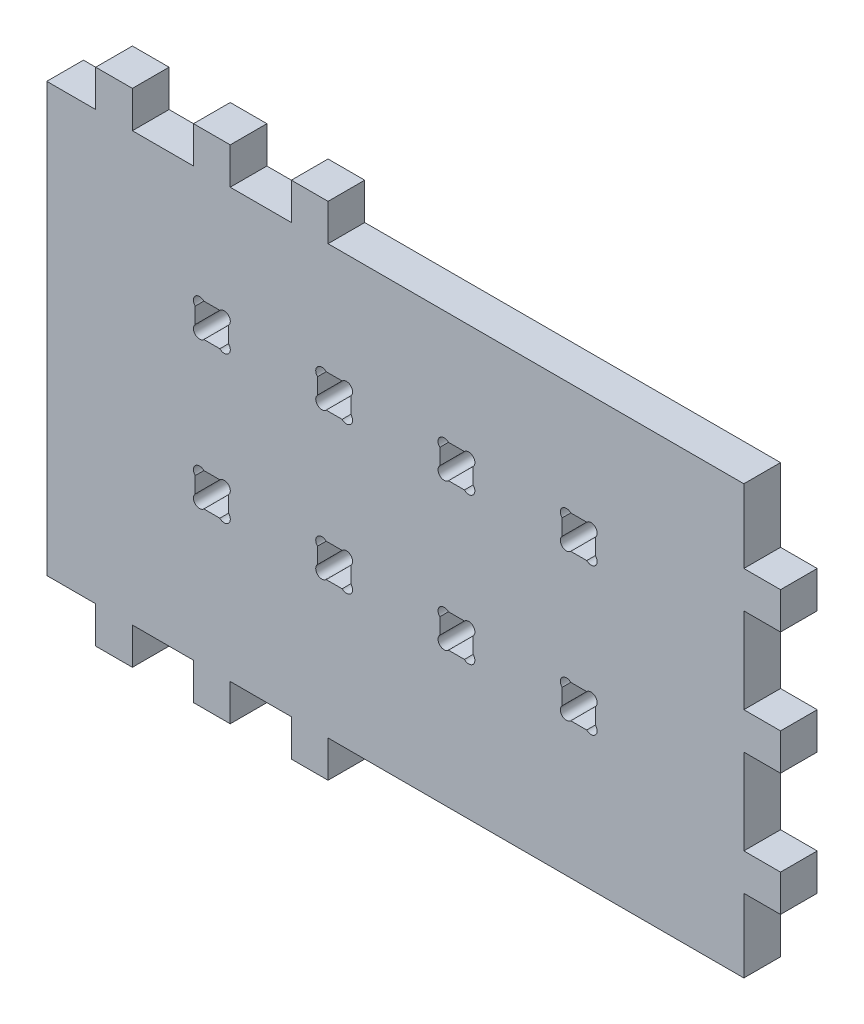
SolidWorks part; units mm, degrees
material "Balsa"
ref_plane "Front Plane" through (0, 0, 0) normal (0, 0, 1) x (1, 0, 0)
ref_plane "Top Plane" through (0, 0, 0) normal (0, 1, 0) x (1, 0, 0)
ref_plane "Right Plane" through (0, 0, 0) normal (1, 0, 0) x (0, 0, -1)
sketch "Sketch1" plane through (0, 0, 0) normal (0, 0, 1) x (1, 0, 0)
  line L1 (0, 0) -> (361.95, 0)
  line L2 (0, 0) -> (0, 222.25)
  line L3 (0, 222.25) -> (361.95, 222.25)
  line L4 (361.95, 0) -> (361.95, 222.25)
  dimension "D1" = 361.95
  dimension "D2" = 222.25
extrude "Boss-Extrude1" add sketch "Sketch1" against normal blind 19.05
sketch "Sketch2" plane through (0, 0, 0) normal (0, 0, 1) x (1, 0, 0)
  line L0 (0, 152.4) -> (361.95, 152.4)
  line L3 (0, 82.55) -> (361.95, 82.55)
  line L4 (0, 12.7) -> (361.95, 12.7) construction
  line L6 (0, 0) -> (361.95, 0) construction
  line L7 (0, 222.25) -> (0, 0) construction
  line L8 (361.95, 0) -> (361.95, 222.25) construction
  line L9 (0, 152.4) -> (-25.4, 152.4)
  line L10 (0, 82.55) -> (-25.4, 82.55)
  line L11 (0, 12.7) -> (-25.4, 12.7) construction
  line L12 (361.95, 12.7) -> (387.35, 12.7) construction
  line L13 (361.95, 82.55) -> (387.35, 82.55)
  line L14 (361.95, 152.4) -> (387.35, 152.4)
  dimension "D1" = 69.85
  dimension "D2" = 69.85
  dimension "D3" = 69.85
  dimension "5" = 0
  dimension "D4" = 25.4
  dimension "D5" = 12.7
sketch "Sketch3" plane through (0, 0, 0) normal (0, 0, 1) x (1, 0, 0)
  line L0 (44.45, 241.3) -> (76.2, 241.3) construction
  line L5 (95.25, 241.3) -> (127, 241.3) construction
  line L10 (361.95, 222.25) -> (0, 222.25) construction
  line L11 (25.4, 222.25) -> (44.45, 222.25)
  line L12 (25.4, 222.25) -> (25.4, 241.3)
  line L13 (25.4, 241.3) -> (44.45, 241.3)
  line L14 (44.45, 222.25) -> (44.45, 241.3)
  line L16 (0, 222.25) -> (0, 0) construction
  line L18 (76.2, 222.25) -> (95.25, 222.25)
  line L19 (76.2, 222.25) -> (76.2, 241.3)
  line L20 (76.2, 241.3) -> (95.25, 241.3)
  line L21 (95.25, 222.25) -> (95.25, 241.3)
  line L22 (146.05, 222.25) -> (127, 222.25)
  line L23 (146.05, 222.25) -> (146.05, 241.3)
  line L24 (146.05, 241.3) -> (127, 241.3)
  line L25 (127, 222.25) -> (127, 241.3)
  dimension "D1" = 19.05
  dimension "D2" = 25.4
  dimension "D3" = 127
extrude "Boss-Extrude4" add sketch "Sketch3" along direction (0, 0, -1) on the side against the normal up to surface (19.05 mm away) up to face at (180.975, 111.125, -19.05)
ref_plane "Plane1" through (0, 111.125, 0) normal (0, 1, 0) x (1, 0, 0)
mirror "Mirror1" about plane through (0, 111.125, 0) normal (0, 1, 0) of "Boss-Extrude4"
ref_plane "Plane2" through (0, 0, -9.525) normal (0, 0, 1) x (1, 0, 0)
sketch "Sketch5" plane through (0, 0, 0) normal (0, 0, 1) x (1, 0, 0)
  line L0 (361.95, 0) -> (361.95, 222.25) construction
  line L1 (361.95, 184.15) -> (381, 184.15)
  line L2 (361.95, 184.15) -> (361.95, 165.1)
  line L3 (361.95, 165.1) -> (381, 165.1)
  line L4 (381, 184.15) -> (381, 165.1)
  line L5 (361.95, 0) -> (361.95, 222.25) construction
  line L6 (361.95, 38.1) -> (381, 38.1)
  line L7 (361.95, 38.1) -> (361.95, 57.15)
  line L8 (361.95, 57.15) -> (381, 57.15)
  line L9 (381, 38.1) -> (381, 57.15)
  line L10 (361.95, 222.25) -> (361.95, 184.15) construction
  line L11 (361.95, 0) -> (361.95, 38.1) construction
  line L12 (361.95, 0) -> (361.95, 222.25) construction
  line L13 (361.95, 120.65) -> (381, 120.65)
  line L14 (361.95, 120.65) -> (361.95, 101.6)
  line L15 (361.95, 101.6) -> (381, 101.6)
  line L16 (381, 120.65) -> (381, 101.6)
  dimension "D1" = 19.05
  dimension "D2" = 38.1
  dimension "D3" = 44.45
  dimension "D4" = 38.1
extrude "Boss-Extrude5" add sketch "Sketch5" against normal up to surface (19.05 mm away) up to face at (99.3321, 111.125, -19.05)
sketch "Sketch6" plane through (0, 0, 0) normal (0, 0, 1) x (1, 0, 0)
  line L0 (0, 222.25) -> (0, 0) construction
  line L5 (77.0815, 88.0028) -> (77.0815, 88.3464)
  line L65 (44.45, -19.05) -> (25.4, -19.05) construction
  line L91 (127, 222.25) -> (95.25, 222.25) construction
  line L92 (81.5716, 70.7308) -> (89.8633, 70.7308)
  line L93 (77.0815, 75.221) -> (77.0815, 83.5127)
  line L94 (81.5716, 88.0028) -> (89.8633, 88.0028)
  line L95 (94.3535, 75.221) -> (94.3535, 83.5127)
  line L96 (145.0716, 88.0028) -> (153.3633, 88.0028)
  line L97 (157.8535, 75.221) -> (157.8535, 83.5127)
  line L98 (145.0716, 70.7308) -> (153.3633, 70.7308)
  line L99 (140.5815, 75.221) -> (140.5815, 83.5127)
  line L100 (208.5716, 88.0028) -> (216.8633, 88.0028)
  line L101 (221.3535, 75.221) -> (221.3535, 83.5127)
  line L102 (208.5716, 70.7308) -> (216.8633, 70.7308)
  line L103 (204.0815, 75.221) -> (204.0815, 83.5127)
  line L104 (272.0716, 88.0028) -> (280.3633, 88.0028)
  line L105 (284.8535, 75.221) -> (284.8535, 83.5127)
  line L106 (272.0716, 70.7308) -> (280.3633, 70.7308)
  line L107 (267.5815, 75.221) -> (267.5815, 83.5127)
  line L108 (145.0716, 164.2028) -> (153.3633, 164.2028)
  line L109 (157.8535, 151.421) -> (157.8535, 159.7127)
  line L110 (145.0716, 146.9308) -> (153.3633, 146.9308)
  line L111 (140.5815, 151.421) -> (140.5815, 159.7127)
  line L112 (208.5716, 164.2028) -> (216.8633, 164.2028)
  line L113 (221.3535, 151.421) -> (221.3535, 159.7127)
  line L114 (208.5716, 146.9308) -> (216.8633, 146.9308)
  line L115 (204.0815, 151.421) -> (204.0815, 159.7127)
  line L116 (272.0716, 164.2028) -> (280.3633, 164.2028)
  line L117 (284.8535, 151.421) -> (284.8535, 159.7127)
  line L118 (272.0716, 146.9308) -> (280.3633, 146.9308)
  line L119 (267.5815, 151.421) -> (267.5815, 159.7127)
  line L120 (81.5716, 164.2028) -> (89.8633, 164.2028)
  line L121 (94.3535, 151.421) -> (94.3535, 159.7127)
  line L122 (81.5716, 146.9308) -> (89.8633, 146.9308)
  line L123 (77.0815, 151.421) -> (77.0815, 159.7127)
  arc A52 (77.0815, 83.5127) -> (81.5716, 88.0028) centre (79.3265, 85.7578) cw
  arc A53 (89.8633, 88.0028) -> (94.3535, 83.5127) centre (92.1084, 85.7578) cw
  arc A54 (77.0815, 75.221) -> (81.5716, 70.7308) centre (79.3265, 72.9759) ccw
  arc A55 (94.3535, 75.221) -> (89.8633, 70.7308) centre (92.1084, 72.9759) cw
  arc A56 (153.3633, 88.0028) -> (157.8535, 83.5127) centre (155.6084, 85.7578) cw
  arc A57 (157.8535, 75.221) -> (153.3633, 70.7308) centre (155.6084, 72.9759) cw
  arc A58 (140.5815, 75.221) -> (145.0716, 70.7308) centre (142.8265, 72.9759) ccw
  arc A59 (140.5815, 83.5127) -> (145.0716, 88.0028) centre (142.8265, 85.7578) cw
  arc A60 (216.8633, 88.0028) -> (221.3535, 83.5127) centre (219.1084, 85.7578) cw
  arc A61 (221.3535, 75.221) -> (216.8633, 70.7308) centre (219.1084, 72.9759) cw
  arc A62 (204.0815, 75.221) -> (208.5716, 70.7308) centre (206.3265, 72.9759) ccw
  arc A63 (204.0815, 83.5127) -> (208.5716, 88.0028) centre (206.3265, 85.7578) cw
  arc A64 (280.3633, 88.0028) -> (284.8535, 83.5127) centre (282.6084, 85.7578) cw
  arc A65 (284.8535, 75.221) -> (280.3633, 70.7308) centre (282.6084, 72.9759) cw
  arc A66 (267.5815, 75.221) -> (272.0716, 70.7308) centre (269.8265, 72.9759) ccw
  arc A67 (267.5815, 83.5127) -> (272.0716, 88.0028) centre (269.8265, 85.7578) cw
  arc A68 (153.3633, 164.2028) -> (157.8535, 159.7127) centre (155.6084, 161.9578) cw
  arc A69 (157.8535, 151.421) -> (153.3633, 146.9308) centre (155.6084, 149.1759) cw
  arc A70 (140.5815, 151.421) -> (145.0716, 146.9308) centre (142.8265, 149.1759) ccw
  arc A71 (140.5815, 159.7127) -> (145.0716, 164.2028) centre (142.8265, 161.9578) cw
  arc A72 (216.8633, 164.2028) -> (221.3535, 159.7127) centre (219.1084, 161.9578) cw
  arc A73 (221.3535, 151.421) -> (216.8633, 146.9308) centre (219.1084, 149.1759) cw
  arc A74 (204.0815, 151.421) -> (208.5716, 146.9308) centre (206.3265, 149.1759) ccw
  arc A75 (204.0815, 159.7127) -> (208.5716, 164.2028) centre (206.3265, 161.9578) cw
  arc A76 (280.3633, 164.2028) -> (284.8535, 159.7127) centre (282.6084, 161.9578) cw
  arc A77 (284.8535, 151.421) -> (280.3633, 146.9308) centre (282.6084, 149.1759) cw
  arc A78 (267.5815, 151.421) -> (272.0716, 146.9308) centre (269.8265, 149.1759) ccw
  arc A79 (267.5815, 159.7127) -> (272.0716, 164.2028) centre (269.8265, 161.9578) cw
  arc A80 (89.8633, 164.2028) -> (94.3535, 159.7127) centre (92.1084, 161.9578) cw
  arc A81 (94.3535, 151.421) -> (89.8633, 146.9308) centre (92.1084, 149.1759) cw
  arc A82 (77.0815, 151.421) -> (81.5716, 146.9308) centre (79.3265, 149.1759) ccw
  arc A83 (77.0815, 159.7127) -> (81.5716, 164.2028) centre (79.3265, 161.9578) cw
  point P0 (85.725, 79.375)
  point P6 (85.7175, 79.3668)
  point P24 (94.3535, 79.3668)
  point P25 (85.7175, 88.0028)
  dimension "D5" = 6.35
  dimension "D3" = 3.175
  dimension "D1" = 85.725
  dimension "D2" = 142.875
  dimension "D6" = 6.35
  dimension "D7" = 6.35
extrude "Cut-Extrude2" cut sketch "Sketch6" against normal through all both contours A55 L95 A53 L94 A52 L93 A54 L92 | A59 L99 A58 L98 A57 L97 A56 L96 | A63 L103 A62 L102 A61 L101 A60 L100 | A67 L107 A66 L106 A65 L105 A64 L104 | A79 L119 A78 L118 A77 L117 A76 L116 | A75 L115 A74 L114 A73 L113 A72 L112 | A71 L111 A70 L110 A69 L109 A68 L108 | A83 L123 A82 L122 A81 L121 A80 L120 region at (85.7175, 79.3668, 0) region at (149.2175, 79.3668, 0) region at (212.7175, 79.3668, 0) region at (276.2175, 79.3668, 0) region at (149.2175, 155.5668, 0) region at (212.7175, 155.5668, 0) region at (276.2175, 155.5668, 0) region at (85.7175, 155.5668, 0)
equation "\"ShelfSpacing\"=2.75"
equation "\"D1@Sketch2\"=\"ShelfSpacing\""
equation "\"D2@Sketch2\"=\"ShelfSpacing\""
equation "\"D3@Sketch2\"=\"ShelfSpacing\""
